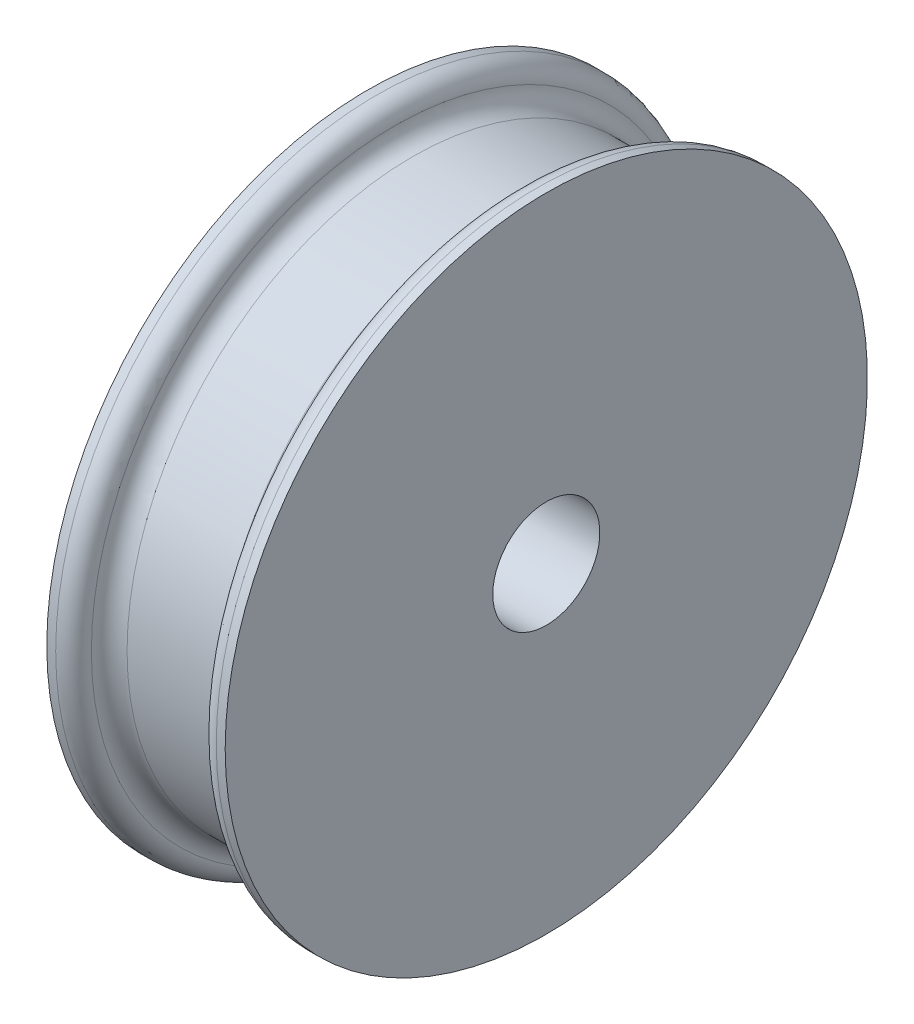
SolidWorks part; units mm, degrees
ref_plane "Front" through (0, 0, 0) normal (0, 0, 1) x (1, 0, 0)
ref_plane "Top" through (0, 0, 0) normal (0, 1, 0) x (1, 0, 0)
ref_plane "Right" through (0, 0, 0) normal (1, 0, 0) x (0, 0, -1)
sketch "Sketch1" plane through (0, 0, 0) normal (0, 0, 1) x (1, 0, 0)
  line L0 (-2.5, 1.5) -> (2.5, 1.5)
  line L1 (2.5, 1.5) -> (2.5, 9)
  line L2 (2.5, 9) -> (1.75, 9)
  line L3 (1.75, 9) -> (1.75, 8.5)
  line L4 (1.25, 8) -> (-1.25, 8)
  line L5 (0, 8) -> (0, 1.5) construction
  line L6 (0, 0) -> (4.984, 0) construction
  line L7 (-1.75, 9) -> (-1.75, 8.5)
  line L8 (-2.5, 9) -> (-1.75, 9)
  line L9 (-2.5, 1.5) -> (-2.5, 9)
  arc A0 (1.75, 8.5) -> (1.25, 8) centre (1.25, 8.5) cw
  arc A1 (-1.75, 8.5) -> (-1.25, 8) centre (-1.25, 8.5) ccw
  point P9 (0, 8)
  point P16 (1.75, 8)
  point P19 (-1.75, 8)
  dimension "D6" = 0.5
  dimension "D1" = 3
  dimension "D2" = 16
  dimension "D3" = 1
  dimension "D4" = 2.5
  dimension "D5" = 0.75
revolve "Revolve1" add sketch "Sketch1" angle 360 about L6
ref_point "Point1"
fillet "Fillet1" radius 0.5 2 edges at (-1.75, 0, 9) (1.75, 0, 9)
